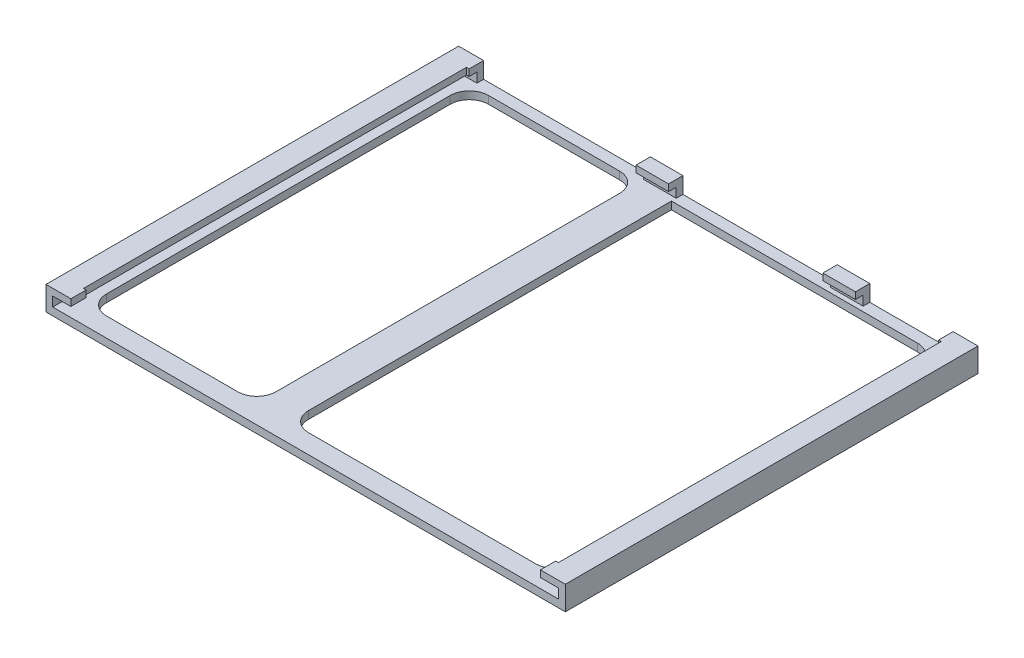
SolidWorks part; units mm, degrees
ref_plane "Front Plane" through (0, 0, 0) normal (0, 0, 1) x (1, 0, 0)
ref_plane "Top Plane" through (0, 0, 0) normal (0, 1, 0) x (1, 0, 0)
ref_plane "Right Plane" through (0, 0, 0) normal (1, 0, 0) x (0, 0, -1)
sketch "Sketch1" plane through (0, 0, 0) normal (0, 0, 1) x (1, 0, 0)
  line L0 (-61.3, -24.209) -> (-61.3, -22.459)
  line L1 (-61.3, -22.459) -> (-67.8, -22.459)
  line L2 (-67.8, -22.459) -> (-67.8, -28.709)
  line L3 (-67.8, -28.709) -> (67.8, -28.709)
  line L4 (67.8, -28.709) -> (67.8, -22.459)
  line L5 (67.8, -22.459) -> (61.3, -22.459)
  line L6 (61.3, -22.459) -> (61.3, -24.209)
  line L7 (61.3, -24.209) -> (66.05, -24.209)
  line L8 (66.05, -24.209) -> (66.05, -26.709)
  line L9 (66.05, -26.709) -> (-66.05, -26.709)
  line L10 (-66.05, -26.709) -> (-66.05, -24.209)
  line L11 (-66.05, -24.209) -> (-61.3, -24.209)
  point P12 (-63.675, -24.209)
  point P15 (0, -28.709)
  dimension "D1" = 132.1
  dimension "D2" = 2
  dimension "D3" = 2.5
  dimension "D4" = 1.75
  dimension "D5" = 1.75
  dimension "D6" = 1.75
  dimension "D7" = 4.75
  dimension "D8" = 4.75
extrude "Boss-Extrude1" add sketch "Sketch1" against normal blind 107.75
sketch "Sketch2" plane through (0, -26.709, 0) normal (0, 1, 0) x (1, 0, 0)
  line L0 (66.05, 107.75) -> (-66.05, 107.75) construction
  line L1 (-17.75, 107.75) -> (-9.25, 107.75)
  line L2 (-17.75, 107.75) -> (-17.75, 102.75)
  line L3 (-17.75, 102.75) -> (-9.25, 102.75)
  line L4 (-9.25, 107.75) -> (-9.25, 102.75)
  line L5 (-66.05, 107.75) -> (-66.05, 0) construction
  line L6 (31.05, 107.75) -> (39.55, 107.75)
  line L7 (31.05, 107.75) -> (31.05, 102.75)
  line L8 (31.05, 102.75) -> (39.55, 102.75)
  line L9 (39.55, 107.75) -> (39.55, 102.75)
  line L10 (66.05, 107.75) -> (66.05, 0) construction
  dimension "D1" = 48.3
  dimension "D2" = 8.5
  dimension "D3" = 26.5
  dimension "D4" = 8.5
  dimension "D5" = 5
extrude "Boss-Extrude2" add sketch "Sketch2" along normal blind 4.25
sketch "Sketch3" plane through (0, 0, -102.75) normal (0, 0, 1) x (1, 0, 0)
  line L0 (-9.25, -22.459) -> (-9.25, -26.709) construction
  line L1 (-17.75, -26.709) -> (-9.25, -26.709)
  line L2 (-17.75, -26.709) -> (-17.75, -24.209)
  line L3 (-17.75, -24.209) -> (-9.25, -24.209)
  line L4 (-9.25, -26.709) -> (-9.25, -24.209)
  line L5 (39.55, -22.459) -> (39.55, -26.709) construction
  line L6 (31.05, -26.709) -> (39.55, -26.709)
  line L7 (31.05, -26.709) -> (31.05, -24.209)
  line L8 (31.05, -24.209) -> (39.55, -24.209)
  line L9 (39.55, -26.709) -> (39.55, -24.209)
  dimension "D1" = 2.5
extrude "Cut-Extrude1" cut sketch "Sketch3" against normal blind 3.25
sketch "Sketch4" plane through (66.05, 0, 0) normal (-1, 0, 0) x (0, 0, 1)
  line L0 (-107.75, -24.209) -> (0, -24.209) construction
  line L1 (-107.75, -26.709) -> (-106, -26.709)
  line L2 (-107.75, -26.709) -> (-107.75, -24.209)
  line L3 (-107.75, -24.209) -> (-106, -24.209)
  line L4 (-106, -26.709) -> (-106, -24.209)
  dimension "D1" = 1.75
extrude "Boss-Extrude3" add sketch "Sketch4" along normal up to surface (4.75 mm away) up to face at (61.3, -23.334, -53.875)
sketch "Sketch5" plane through (-66.05, 0, 0) normal (1, 0, 0) x (0, 0, -1)
  line L0 (107.75, -24.209) -> (0, -24.209) construction
  line L1 (107.75, -26.709) -> (106, -26.709)
  line L2 (107.75, -26.709) -> (107.75, -24.209)
  line L3 (107.75, -24.209) -> (106, -24.209)
  line L4 (106, -26.709) -> (106, -24.209)
  dimension "D1" = 1.75
extrude "Boss-Extrude4" add sketch "Sketch5" along normal up to surface (4.75 mm away) up to face at (-61.3, -23.334, -53.875)
sketch "Sketch6" plane through (0, -28.709, 0) normal (0, -1, 0) x (1, 0, 0)
  line L0 (-67.8, -107.75) -> (-67.8, 0) construction
  line L1 (-62, -104) -> (62, -104)
  line L2 (-62, -104) -> (-62, -4)
  line L3 (-62, -4) -> (62, -4)
  line L4 (62, -104) -> (62, -4)
  line L6 (-67.8, 0) -> (67.8, 0) construction
  dimension "D1" = 124
  dimension "D2" = 100
  dimension "D3" = 5.8
  dimension "D4" = 4
extrude "Cut-Extrude2" cut sketch "Sketch6" against normal blind 10 from surface starting at face at (5.45, -26.709, -93.4062)
sketch "Sketch7" plane through (0, -28.709, 0) normal (0, -1, 0) x (1, 0, 0)
  line L0 (-67.8, -107.75) -> (-67.8, 0) construction
  line L1 (-62, -5) -> (-17.75, -5)
  line L2 (-62, -5) -> (-62, -104.75)
  line L3 (-62, -104.75) -> (-17.75, -104.75)
  line L4 (59.9852, -5) -> (59.9852, -104.75)
  line L5 (-67.8, 0) -> (67.8, 0) construction
  line L6 (-67.8, -107.75) -> (67.8, -107.75) construction
  line L7 (-9.25, -5) -> (59.9852, -5)
  line L9 (-17.75, -104.75) -> (-17.75, -5)
  line L11 (-9.25, -104.75) -> (-9.25, -5)
  line L12 (-9.25, -104.75) -> (59.9852, -104.75)
  dimension "D1" = 5.8
  dimension "D2" = 5
  dimension "D3" = 3
  dimension "D4" = 0
  dimension "D5" = 0
extrude "Cut-Extrude4" cut sketch "Sketch7" against normal up to surface (2 mm away) up to face at (5.45, -26.709, -93.4062)
fillet "Fillet2" radius 5 7 edges at (59.9852, -27.709, -5) (59.9852, -27.709, -104.75) (-62, -27.709, -104.75) (-62, -27.709, -5) (-9.25, -27.709, -5) (-17.75, -27.709, -5) (-17.75, -27.709, -104.75)
